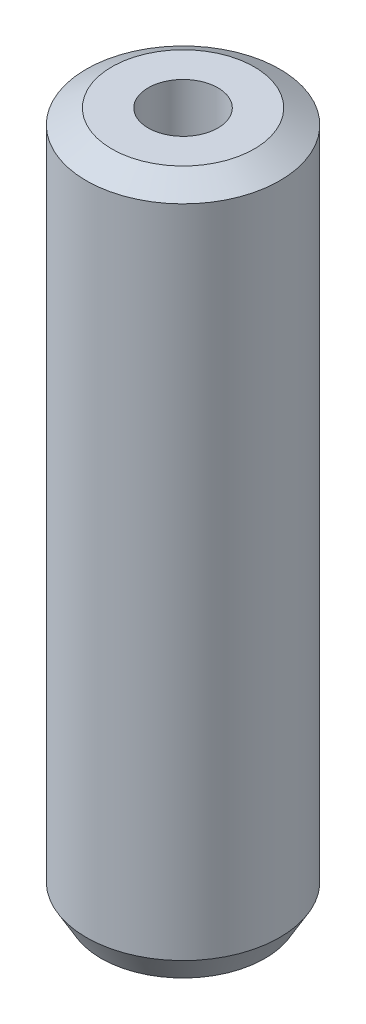
SolidWorks part; units mm, degrees
ref_plane "Front Plane" through (0, 0, 0) normal (0, 0, 1) x (1, 0, 0)
ref_plane "Top Plane" through (0, 0, 0) normal (0, 1, 0) x (1, 0, 0)
ref_plane "Right Plane" through (0, 0, 0) normal (1, 0, 0) x (0, 0, -1)
sketch "Sketch1" plane through (0, 0, 0) normal (0, 1, 0) x (1, 0, 0)
  circle A0 centre (0, 0) radius 35
  dimension "SHAFT_OD" = 70
extrude "Boss-Extrude1" add sketch "Sketch1" along normal blind 251.6964
sketch "Sketch2" plane through (0, 0, 0) normal (0, 1, 0) x (1, 0, 0)
  circle A0 centre (0, 0) radius 12.6173
  dimension "BORE_D" = 25.2345
extrude "Cut-Extrude1" cut sketch "Sketch2" along normal through all
chamfer "Chamfer1" distance 5.331 angle 60 2 edges at (0, 251.6964, 35) (0, 0, 35) first distance on face at (0, 251.6964, 35) first distance on face at (0, 0, 12.6173)
